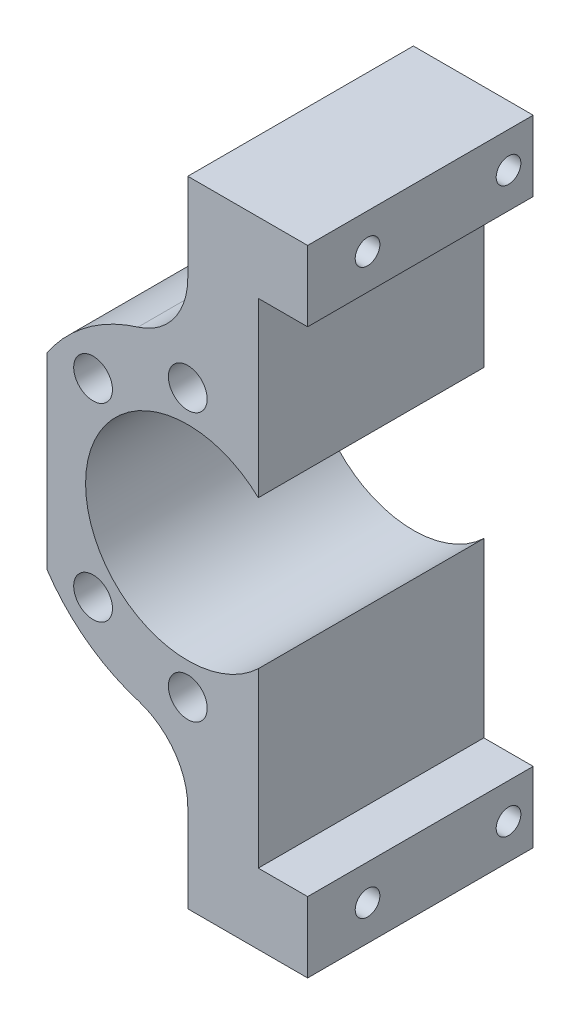
SolidWorks part; units mm, degrees
ref_plane "Plan de face" through (0, 0, 0) normal (0, 0, 1) x (1, 0, 0)
ref_plane "Plan de dessus" through (0, 0, 0) normal (0, 1, 0) x (1, 0, 0)
ref_plane "Plan de droite" through (0, 0, 0) normal (1, 0, 0) x (0, 0, -1)
sketch "Esquisse2" plane through (0, 0, 0) normal (0, 0, 1) x (1, 0, 0)
  line L1 (-22.3865, 12.0572) -> (-22.3865, -14.4758)
  line L2 (-2.3865, 22.7907) -> (7.6135, 22.7907)
  line L5 (7.6135, -25.2093) -> (-2.3865, -25.2093)
  line L6 (7.6135, -11.7093) -> (7.6135, -25.2093)
  line L7 (7.6135, 9.2907) -> (7.6135, 22.7907)
  arc A0 (7.6135, -11.7093) -> (7.6135, 9.2907) centre (-2.3865, -1.2093) cw
  arc A2 (-22.3865, 12.0572) -> (-2.3865, 22.7907) centre (-2.3865, -1.2093) cw
  arc A3 (-22.3865, -14.4758) -> (-2.3865, -25.2093) centre (-2.3865, -1.2093) ccw
  circle A4 centre (-2.3865, -1.2093) radius 19 construction
  circle A5 centre (-2.3865, 17.7907) radius 2.75
  circle A6 centre (-15.8215, 12.2258) radius 2.75
  circle A8 centre (-2.3865, -20.2093) radius 2.75
  circle A10 centre (-15.8215, -14.6443) radius 2.75
  dimension "D2" = 24
  dimension "D3" = 38
  dimension "D4" = 5.5
  dimension "D5" = 30
  dimension "D9" = 14.5
  dimension "D1" = 26.533
  dimension "D6" = 45
  dimension "D8" = 45
extrude "Boss.-Extru.1" add sketch "Esquisse2" along normal blind 32
sketch "Esquisse3" plane through (7.6135, 0, 0) normal (1, 0, 0) x (0, 0, -1)
  line L1 (0, 22.7907) -> (-32, 22.7907)
  line L2 (-32, 22.7907) -> (-32, 43.7907)
  line L3 (-32, 43.7907) -> (0, 43.7907)
  line L4 (0, 43.7907) -> (0, 22.7907)
  line L5 (0, -25.2093) -> (0, -11.7093) construction
  line L6 (-32, -25.2093) -> (0, -25.2093)
  line L7 (-32, -25.2093) -> (-32, -46.2093)
  line L8 (-32, -46.2093) -> (0, -46.2093)
  line L9 (0, -25.2093) -> (0, -46.2093)
  line L10 (-32, 22.7907) -> (-32, -25.2093) construction
  line L11 (-23.5, 38.7907) -> (-23.5, -41.2093) construction
  circle A0 centre (-23.5, 38.7907) radius 1.75
  circle A1 centre (-3.5, 38.7907) radius 1.75
  circle A2 centre (-23.5, -41.2093) radius 1.75
  circle A3 centre (-3.5, -41.2093) radius 1.75
  point P21 (-23.5, -1.2093)
  point P22 (-32, -1.2093)
  point P23 (0, 0)
  point P24 (0, 0)
  point P25 (0, 0)
  dimension "D1" = 3.5
  dimension "D2" = 20
  dimension "D3" = 80
  dimension "D4" = 5
  dimension "D5" = 3.5
extrude "Boss.-Extru.2" add sketch "Esquisse3" against normal up to vertex (10 mm away) up to point (-2.3865, 22.7907, 32)
sketch "Esquisse4" plane through (7.6135, 0, 0) normal (1, 0, 0) x (0, 0, -1)
  line L0 (0, 9.2907) -> (0, 43.7907) construction
  line L1 (-32, 43.7907) -> (0, 43.7907)
  line L2 (-32, 43.7907) -> (-32, 33.7907)
  line L3 (-32, 33.7907) -> (0, 33.7907)
  line L4 (0, 43.7907) -> (0, 33.7907)
  line L5 (0, -46.2093) -> (0, -11.7093) construction
  line L6 (-32, -46.2093) -> (0, -46.2093)
  line L7 (-32, -46.2093) -> (-32, -36.2093)
  line L8 (-32, -36.2093) -> (0, -36.2093)
  line L9 (0, -46.2093) -> (0, -36.2093)
  circle A0 centre (-3.5, -41.2093) radius 1.75 construction
  circle A1 centre (-23.5, -41.2093) radius 1.75 construction
  circle A2 centre (-3.5, 38.7907) radius 1.75 construction
  circle A3 centre (-23.5, 38.7907) radius 1.75 construction
  circle A4 centre (-3.5, -41.2093) radius 1.75
  circle A5 centre (-23.5, -41.2093) radius 1.75
  circle A6 centre (-3.5, 38.7907) radius 1.75
  circle A7 centre (-23.5, 38.7907) radius 1.75
  dimension "D1" = 10
extrude "Boss.-Extru.3" add sketch "Esquisse4" along normal blind 7
fillet "Congé1" radius 10 2 edges at (-2.3865, -25.2093, 16) (-2.3865, 22.7907, 16)
